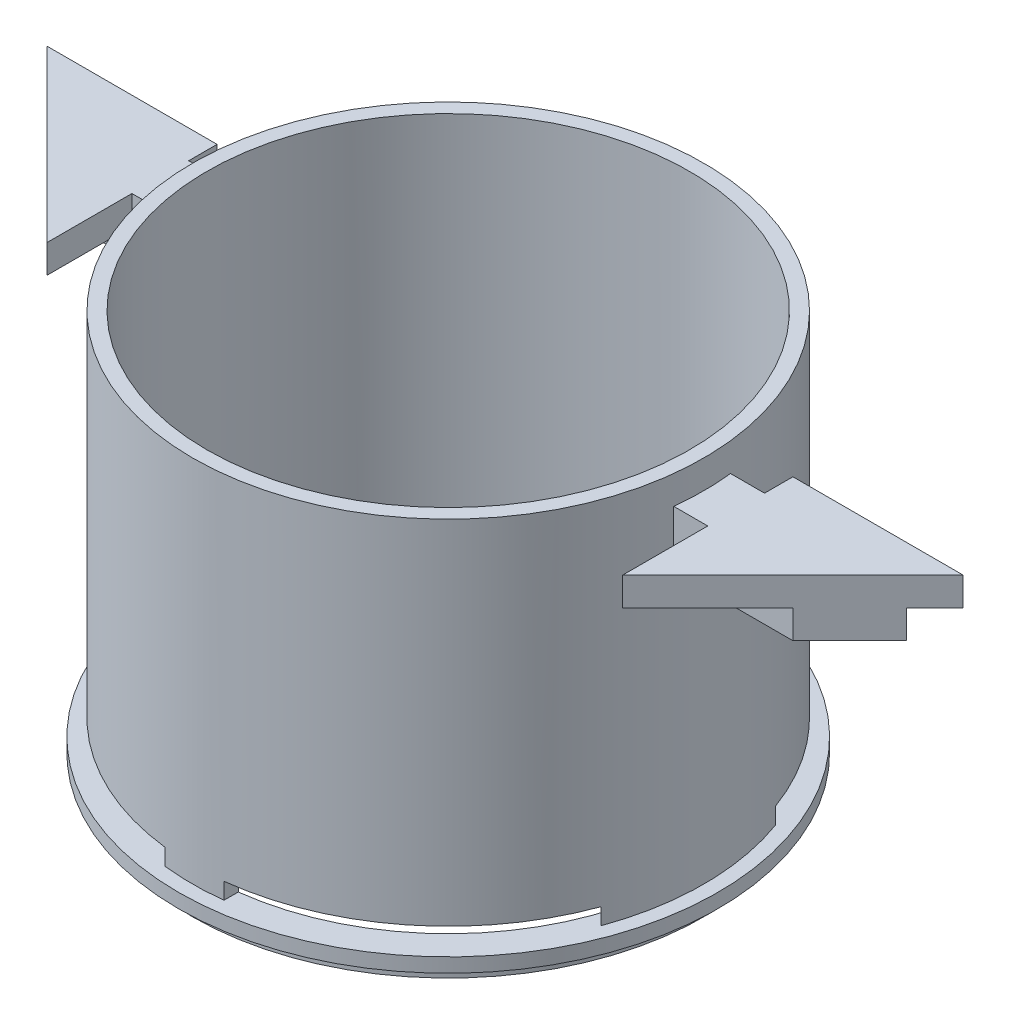
SolidWorks part; units mm, degrees
ref_plane "Front Plane" through (0, 0, 0) normal (0, 0, 1) x (1, 0, 0)
ref_plane "Top Plane" through (0, 0, 0) normal (0, 1, 0) x (1, 0, 0)
ref_plane "Right Plane" through (0, 0, 0) normal (1, 0, 0) x (0, 0, -1)
sketch "Sketch1" plane through (0, 0, 0) normal (0, 1, 0) x (1, 0, 0)
  circle A0 centre (0, 0) radius 57.15
  dimension "D2" = 114.3
extrude "Boss-Extrude1" add sketch "Sketch1" along normal blind 88.9
sketch "Sketch2" plane through (0, 88.9, 0) normal (0, 1, 0) x (1, 0, 0)
  circle A0 centre (0, 0) radius 53.975
  circle A1 centre (0, 0) radius 57.15 construction
  dimension "D2" = 3.175
extrude "Cut-Extrude1" cut sketch "Sketch2" against normal through all
sketch "Sketch6" plane through (0, 0, 0) normal (0, 0, 1) x (1, 0, 0)
  line L0 (-57.15, 88.9) -> (-57.15, 0) construction
  line L1 (-53.721, 10.033) -> (-6.604, 10.033)
  line L2 (-53.721, 10.033) -> (-53.721, 6.35)
  line L3 (-53.721, 6.35) -> (-6.604, 6.35)
  line L7 (-53.975, 0) -> (53.975, 0) construction
  line L8 (-6.604, 10.033) -> (-6.604, 6.35)
  line L9 (0, 0) -> (0, 21.9448) construction
  line L10 (6.604, 10.033) -> (6.604, 6.35)
  line L11 (53.721, 6.35) -> (6.604, 6.35)
  line L12 (53.721, 10.033) -> (6.604, 10.033)
  line L13 (53.721, 10.033) -> (53.721, 6.35)
  dimension "D2" = 3.429
  dimension "D3" = 3.683
  dimension "D4" = 6.35
  dimension "D1" = 6.604
extrude "Cut-Extrude4" cut sketch "Sketch6" against normal through all both and the other way through all
ref_plane "Plane1" through (0, 69.85, 0) normal (0, 1, 0) x (1, 0, 0)
sketch "Sketch10" plane through (0, 0, 0) normal (0, 1, 0) x (1, 0, 0)
  circle A0 centre (0, 0) radius 60.325
  circle A1 centre (0, 0) radius 57.15 construction
  circle A2 centre (0, 0) radius 57.15
  dimension "D1" = 120.65
extrude "Boss-Extrude7" add sketch "Sketch10" along normal blind 3.175 from offset 3.175
sketch "Sketch9" plane through (0, 69.85, 0) normal (0, 1, 0) x (1, 0, 0)
  line L1 (-83.4526, -6.35) -> (-53.6002, -6.35)
  line L3 (-96.1526, 6.35) -> (-53.6002, 6.35)
  line L7 (-96.1526, 6.35) -> (-83.4526, -6.35)
  circle A0 centre (0, 0) radius 53.975 construction
  arc A1 (-53.6002, 6.35) -> (-53.6002, -6.35) centre (0, 0) ccw
  point P0 (0, 0)
  point P2 (-89.8026, 0)
  dimension "D1" = 96.1526
  dimension "D2" = 45
  dimension "D4" = 12.7
extrude "Boss-Extrude6" add sketch "Sketch9" along normal blind 12.7
sketch "Sketch11" plane through (0, 82.55, 0) normal (0, 1, 0) x (1, 0, 0)
  line L0 (-64.4026, -25.4) -> (-64.4026, 12.7)
  line L1 (-64.4026, 12.7) -> (-102.5026, 12.7)
  line L2 (-102.5026, 12.7) -> (-64.4026, -25.4)
  line L3 (-96.1526, 6.35) -> (-83.4526, -6.35) construction
  line L4 (-56.7961, 6.35) -> (-96.1526, 6.35) construction
  line L5 (-83.4526, -6.35) -> (-56.7961, -6.35) construction
  dimension "D1" = 6.35
  dimension "D2" = 19.05
extrude "Boss-Extrude8" add sketch "Sketch11" against normal blind 6.35
mirror "Mirror1" about plane through (0, 0, 0) normal (1, 0, 0) of "Boss-Extrude6", "Boss-Extrude8"
equation "\"tightTol\" = 0.005in"
equation "\"normTol\"= 0.01in"
equation "\"looseTol\"= 0.02in"
equation "\"D2@Sketch6\"=\"normTol\"+0.125000in"
equation "\"D1@Sketch6\"=\"normTol\"+0.250000in"
equation "\"D3@Sketch6\"=\"looseTol\"+0.125000in"
